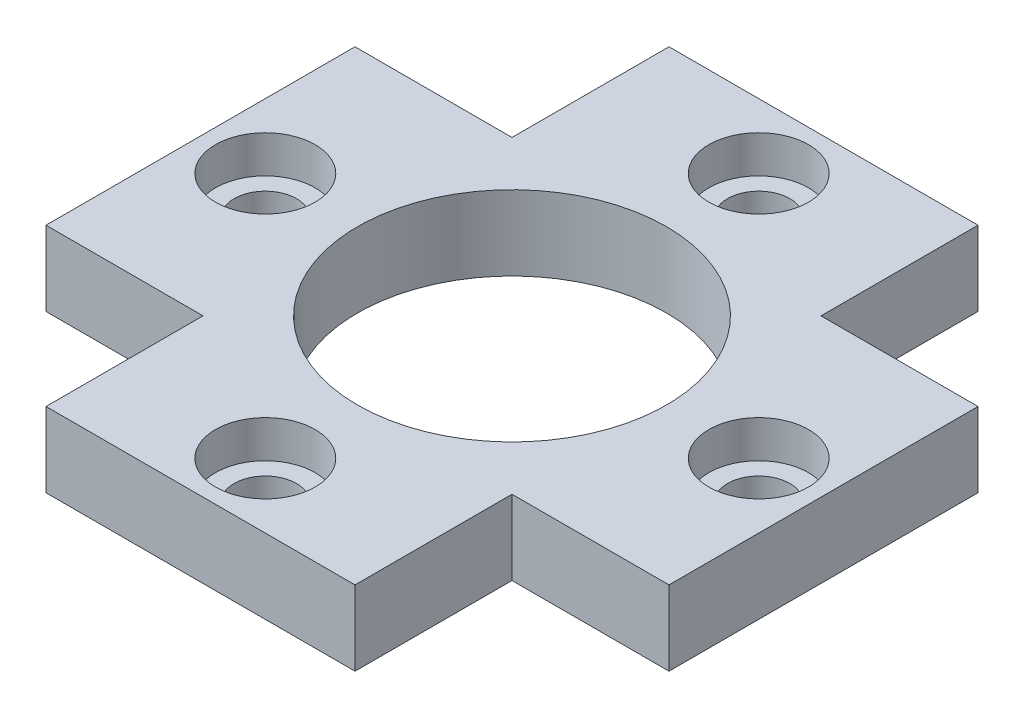
SolidWorks part; units mm, degrees
ref_plane "前视基准面" through (0, 0, 0) normal (0, 0, 1) x (1, 0, 0)
ref_plane "上视基准面" through (0, 0, 0) normal (0, 1, 0) x (1, 0, 0)
ref_plane "右视基准面" through (0, 0, 0) normal (1, 0, 0) x (0, 0, -1)
other "Configuration Table"
sketch "草图1" plane through (0, 0, 0) normal (0, 1, 0) x (1, 0, 0)
  line L1 (-12.5, -6.2) -> (12.5, -6.2)
  line L2 (-12.5, -6.2) -> (-12.5, 6.2)
  line L3 (-12.5, 6.2) -> (12.5, 6.2)
  line L4 (12.5, -6.2) -> (12.5, 6.2)
  line L5 (-12.5, -6.2) -> (12.5, 6.2) construction
  line L6 (-12.5, 6.2) -> (12.5, -6.2) construction
  line L7 (-6.2, -12.5) -> (6.2, -12.5)
  line L8 (-6.2, -12.5) -> (-6.2, 12.5)
  line L9 (-6.2, 12.5) -> (6.2, 12.5)
  line L10 (6.2, -12.5) -> (6.2, 12.5)
  line L11 (-6.2, -12.5) -> (6.2, 12.5) construction
  line L12 (-6.2, 12.5) -> (6.2, -12.5) construction
  circle A18 centre (0, 0) radius 6.2
  dimension "D3" = 25
  dimension "D1" = 12.4
  dimension "D2" = 12.4
extrude "凸台-拉伸1" add sketch "草图1" along normal blind 3 contours A18 L10 L3 | A18 L3 L8 | A18 L8 L1 | A18 L1 L10 | L7 L10 L1 L8 | L10 L1 L4 L3 | L3 L10 L9 L8 | L1 L8 L3 L2 region at (-9.35, 0, 0) region at (-4.8151, 0, 4.8151) region at (0, 0, 9.35) region at (4.8151, 0, 4.8151) region at (-4.8151, 0, -4.8151) region at (0, 0, -9.35) region at (9.35, 0, 0) region at (4.8151, 0, -4.8151)
sketch "草图2" plane through (0, 0, 0) normal (0, -1, 0) x (-1, 0, 0)
  line L0 (-12.5, -6.2) -> (-12.5, 6.2) construction
  circle A0 centre (-9.8995, 0) radius 2
  circle A1 centre (-9.8995, 0) radius 1.25
  circle A2 centre (-8.5, 0) radius 2
  circle A3 centre (-8.5, 0) radius 1.25
  dimension "D1" = 4
  dimension "D2" = 2.5
  dimension "D3" = 4
extrude "切除-拉伸1" cut sketch "草图2" against normal through all contours A1
extrude "切除-拉伸2" cut sketch "草图2<3>" along normal blind 1.5 from surface contours A0 starting at face at (9.8995, 3, -1.25)
sketch "草图2<3>" plane through (0, 0, 0) normal (0, -1, 0) x (-1, 0, 0) same geometry as "草图2"
pattern_circular "阵列(圆周)1" count 4 over 360 about axis through (0, 3, 0) along (0, -1, 0) of "切除-拉伸1", "切除-拉伸2"
